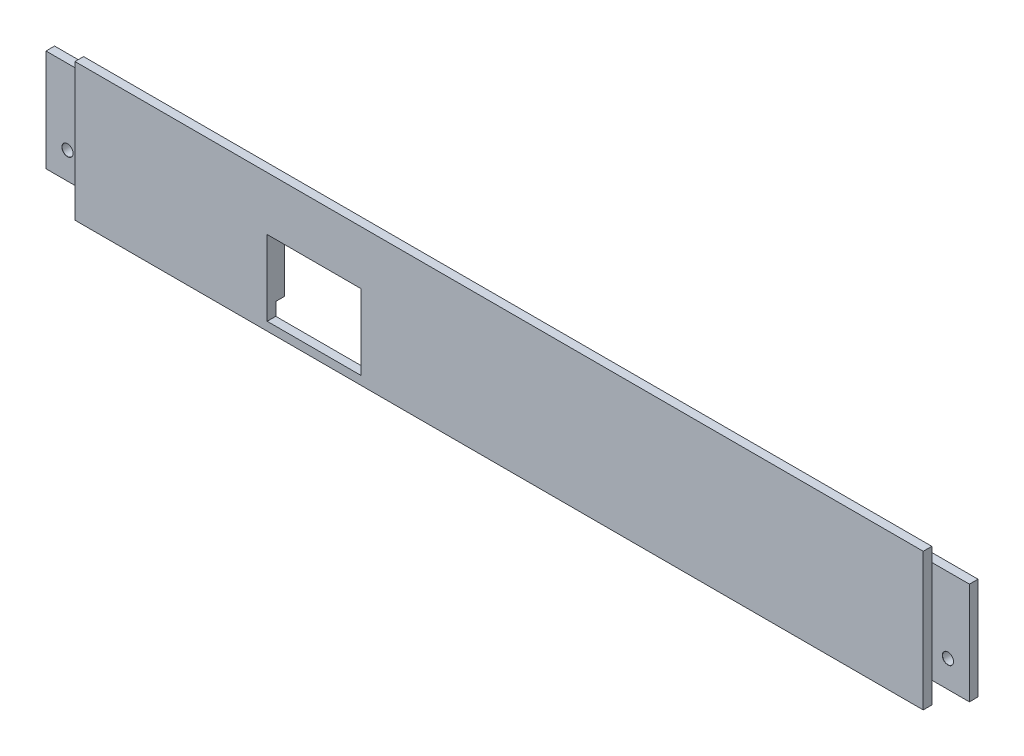
SolidWorks part; units mm, degrees
ref_plane "Front Plane" through (0, 0, 0) normal (0, 0, 1) x (1, 0, 0)
ref_plane "Top Plane" through (0, 0, 0) normal (0, 1, 0) x (1, 0, 0)
ref_plane "Right Plane" through (0, 0, 0) normal (1, 0, 0) x (0, 0, -1)
sketch "Sketch1" plane through (0, 0, 0) normal (0, 0, 1) x (1, 0, 0)
  line L0 (0, -55) -> (0, 55) construction
  line L1 (-79, 25.6) -> (79, 25.6)
  line L2 (-79, 25.6) -> (-79, 0)
  line L3 (-79, 0) -> (79, 0)
  line L4 (79, 25.6) -> (79, 0)
  line L5 (55, 0) -> (-55, 0) construction
  dimension "D1" = 158
  dimension "D2" = 25.6
  dimension "D3" = 79
  dimension "D4" = 0
extrude "Boss-Extrude1" add sketch "Sketch1" along normal blind 1.6
sketch "Sketch2" plane through (0, 0, 0) normal (0, 0, 1) x (1, 0, 0)
  line L0 (-79, 0) -> (79, 0) construction
  line L1 (-86, 23) -> (86, 23)
  line L2 (-86, 23) -> (-86, 4)
  line L3 (-86, 4) -> (86, 4)
  line L4 (86, 23) -> (86, 4)
  line L5 (0, 26.3642) -> (0, -16.9121) construction
  line L6 (-79, 25.6) -> (-79, 0) construction
  dimension "D1" = 172
  dimension "D2" = 19
  dimension "D3" = 4
  dimension "D4" = 79
  dimension "D5" = 86
extrude "Boss-Extrude2" add sketch "Sketch2" against normal blind 1.6
hole_wizard "Tap Drill for M2.5x0.45 Tap3" positions "3DSketch3" profile "Sketch5" hole size "M2.5x0.45" standard "ANSI Metric" end condition through all
sketch3d "3DSketch3"
  point P0 (-82, 9, 0)
  point P3 (82, 9, 0)
  dimension "D1" = 82
  dimension "D2" = 82
  dimension "D3" = 9
  dimension "D4" = 9
sketch "Sketch5" plane through (-82, 9, 0) normal (1, 0, 0) x (0, -1, 0)
  line L0 (0, 0) -> (0, 1.6)
  line L1 (0, 1.6) -> (1.025, 1.6)
  line L2 (1.025, 1.6) -> (1.025, 0.025)
  line L3 (1.025, 0.025) -> (1.05, 0)
  line L5 (1.05, 0) -> (0, 0)
  line L6 (-1.025, 0.025) -> (-1.05, 0) construction
  line L11 (0, -6.35) -> (0, 107.95) construction
  dimension "Thru Hole Dia." = 2.05
  dimension "Thru Hole Depth" = 1.6
  dimension "Near C'Sink Dia." = 2.1
  dimension "Near C'Sink Angle" = 90
ref_plane "PCB top" through (0, 1.6, 0) normal (0, 1, 0) x (1, 0, 0)
sketch "Sketch7" plane through (0, 1.6, 0) normal (0, 1, 0) x (1, 0, 0)
  line L0 (0, -1.76) -> (0, 1.76) construction
  line L1 (-80.9, 68.51) -> (80.9, 68.51) construction
  line L2 (-80.9, 68.51) -> (-80.9, 0.51) construction
  line L3 (-80.9, 0.51) -> (80.9, 0.51) construction
  line L4 (80.9, 68.51) -> (80.9, 0.51) construction
  line L5 (-14.08, 0) -> (14.08, 0) construction
  line L6 (-60.9, 68.51) -> (-60.9, 0) construction
  line L7 (70.9, 68.51) -> (70.9, 0) construction
  line L9 (-60.9, 0) -> (-52.9, 0)
  line L10 (-60.9, 0) -> (-60.9, 7)
  line L11 (-60.9, 7) -> (-52.9, 7)
  line L12 (-52.9, 0) -> (-52.9, 7)
  line L13 (70.9, 0) -> (62.9, 0)
  line L14 (70.9, 0) -> (70.9, 7)
  line L15 (70.9, 7) -> (62.9, 7)
  line L16 (62.9, 0) -> (62.9, 7)
  circle A0 centre (-56.9, 4.51) radius 1.3
  circle A1 centre (66.9, 4.51) radius 1.3
  dimension "D14" = 2.6
  dimension "D15" = 2.6
  dimension "D1" = 80.9
  dimension "D2" = 80.9
  dimension "D3" = 0.51
  dimension "D4" = 68
  dimension "D5" = 20
  dimension "D6" = 10
  dimension "8" = 8
  dimension "D8" = 7
  dimension "D9" = 8
  dimension "D10" = 7
  dimension "D11" = 4
  dimension "D7" = 4
  dimension "D12" = 4
  dimension "D13" = 4
extrude "Boss-Extrude3" add sketch "Sketch7" along normal blind 4 separate body
sketch "Sketch8" plane through (0, 0, 0) normal (0, 0, 1) x (1, 0, 0)
  line L0 (0, -4.73) -> (0, 4.73) construction
  line L1 (-43.2, 15.6) -> (-25.7, 15.6)
  line L2 (-43.2, 15.6) -> (-43.2, 1.6)
  line L3 (-43.2, 1.6) -> (-25.7, 1.6)
  line L4 (-25.7, 15.6) -> (-25.7, 1.6)
  line L5 (4.73, 1.6) -> (-4.73, 1.6) construction
  dimension "D1" = 17.5
  dimension "D2" = 14
  dimension "D3" = 25.7
extrude "Cut-Extrude1" cut sketch "Sketch8" against normal through all both and the other way through all
combine bodies "Combine1" operation type add bodies to combine 106 107 108
fillet "Fillet1" radius 0.5 6 edges at (62.9, 4.8, -1.6) (66.9, 5.6, -1.6) (70.9, 4.8, -1.6) (-52.9, 4.8, -1.6) (-60.9, 4.8, -1.6) (-56.9, 5.6, -1.6)
equation "\"D4@Sketch2\"=158/2"
equation "\"D5@Sketch2\"=172/2"
equation "\"D3@Sketch1\"=158/2"
equation "\"D1\"= 164 / 2"
equation "\"D1@3DSketch3\"=164/2"
equation "\"D2@3DSketch3\"=164/2"
equation "\"D1@Sketch7\"=161.8/2"
equation "\"D2@Sketch7\"=\"D1@Sketch7\""
equation "\"D9@Sketch7\"=\"8@Sketch7\""
equation "\"D10@Sketch7\"=\"D8@Sketch7\""
equation "\"D7@Sketch7\"=\"D11@Sketch7\""
equation "\"D15@Sketch7\"=\"D14@Sketch7\""
equation "\"D13@Sketch7\"=\"D12@Sketch7\""
